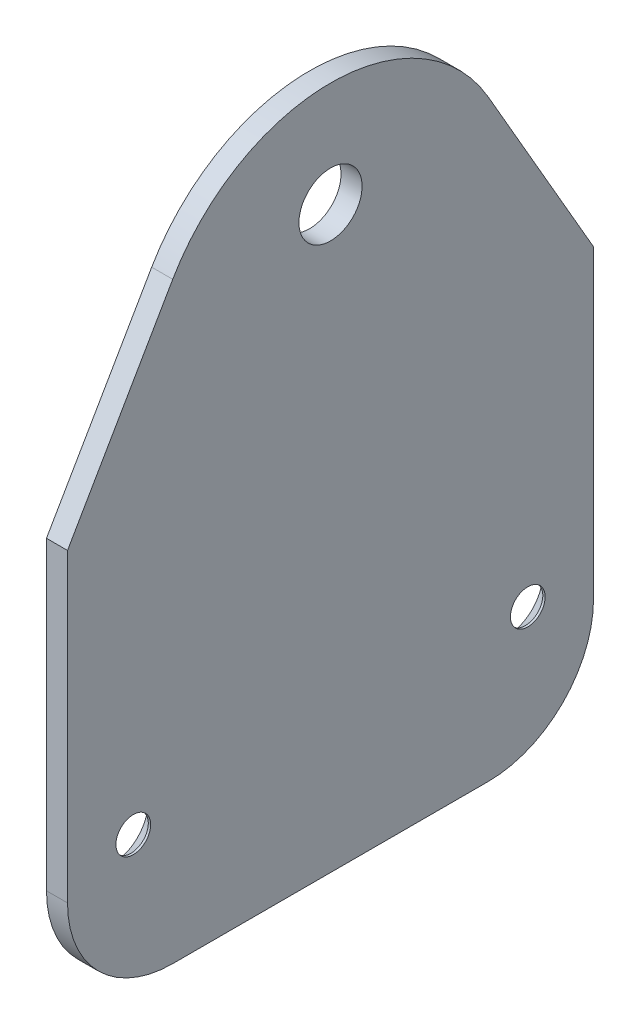
SolidWorks part; units mm, degrees
material "1023 Листовая углеродистая сталь (SS)"
ref_plane "Спереди" through (0, 0, 0) normal (0, 0, 1) x (1, 0, 0)
ref_plane "Сверху" through (0, 0, 0) normal (0, 1, 0) x (1, 0, 0)
ref_plane "Справа" through (0, 0, 0) normal (1, 0, 0) x (0, 0, -1)
sketch "Эскиз1" plane through (0, 0, 0) normal (0, 1, 0) x (1, 0, 0)
  line L1 (20, -45) -> (-20, -45)
  line L2 (20, -45) -> (20, 45)
  line L3 (20, 45) -> (-20, 45)
  line L4 (-20, -45) -> (-20, 45)
  line L5 (20, -45) -> (-20, 45) construction
  line L6 (20, 45) -> (-20, -45) construction
  point P0 (0, 0)
  dimension "D1" = 90
  dimension "D2" = 40
sketch "Эскиз10" plane through (0, 0, 0) normal (1, 0, 0) x (0, 0, -1)
  line L0 (2.2, 0) -> (-2.2, 0) construction
  line L1 (-50, 0) -> (50, 0)
  line L2 (-50, 0) -> (-50, 130)
  line L3 (-50, 130) -> (50, 130)
  line L4 (50, 0) -> (50, 130)
  line L5 (0, 0) -> (0, 50000) construction
  dimension "D1" = 100
  dimension "D2" = 130
base flange "Базовая кромка1" sketch "Эскиз10" thickness 4 reverse thickness direction no parameters "D1"=5
sketch "Эскиз13" plane through (-4, 0, 0) normal (-1, 0, 0) x (0, 0, 1)
  line L1 (-50, 130) -> (50, 130) construction
  circle A0 centre (0, 110) radius 6
  dimension "D2" = 12
  dimension "D1" = 20
extrude "Вырез-Вытянуть1" cut sketch "Эскиз13" against normal blind 10 normal cut yes
sketch "Эскиз17" plane through (-4, 0, 0) normal (-1, 0, 0) x (0, 0, 1)
  line L0 (50, 0) -> (-50, 0) construction
  line L2 (0, 68.9825) -> (0, -30.3252) construction
  point P0 (-37.5, 25)
  point P3 (37.5, 25)
  dimension "D1" = 75
  dimension "D2" = 25
hole_wizard "Зенковка для винта с потайной головкой и внутренним шестигранником M61" positions "Эскиз17" profile "Эскиз16" countersink size "M6" standard "DIN" end condition through all
sketch "Эскиз16" plane through (-4, 25, -37.5) normal (0, 1, 0) x (0, 0, 1)
  line L0 (0, 0) -> (0, 4)
  line L1 (0, 4) -> (3.3, 4)
  line L2 (3.3, 4) -> (3.3, 3.555)
  line L3 (3.3, 3.555) -> (6.855, 0)
  line L5 (6.855, 0) -> (0, 0)
  line L6 (-3.3, 3.555) -> (-6.855, 0) construction
  line L11 (0, -6.35) -> (0, 107.95) construction
  dimension "Диаметр сквозного отверстия" = 6.6
  dimension "Глубина сквозного отверстия" = 4
  dimension "Диаметр передней зенковки" = 13.71
  dimension "Угол передней зенковки" = 90
chamfer "Фаска1" distance 30 angle 60 2 edges at (-2, 130, 50) (-2, 130, -50) first distance on face at (-2, 130, 0)
fillet "Скругление1" radius 34.641 4 edges at (0, 130, 0) (-4, 130, 0) (-2, 130, -20) (-2, 130, 20)
fillet "Скругление2" radius 20 2 edges at (-2, 0, 50) (-2, 0, -50)
sketch "Сгиб-Линии1" [suppressed] plane through (0, 0, 0) normal (0, 1, 0) x (1, 0, 0)
sketch "Граничная рамка1" [suppressed] plane through (0, 0, 0) normal (0, 1, 0) x (1, 0, 0)
sheet metal parameters "Листовой металл4" thickness 4 parameters "D1"=5
flat pattern "Развертка4" [suppressed]
sketch "Сгиб-Линии3" plane through (0, 0, 0) normal (0, 1, 0) x (1, 0, 0)
sketch3d "Граничная рамка3" [suppressed]
  line L0 (-45, 120, 0) -> (-45, 0, 0) construction
  line L1 (45, 120, 0) -> (45, 0, 0) construction
  line L2 (-45, 120, 0) -> (45, 120, 0) construction
  line L3 (-45, 0, 0) -> (45, 0, 0) construction
sheet metal parameters "Листовой металл5" thickness 4 parameters "D1"=5
flat pattern "Развертка4"
sketch "Сгиб-Линии3" plane through (0, 0, 0) normal (0, 1, 0) x (1, 0, 0)
sketch3d "Граничная рамка3" [suppressed]
  line L0 (-45, 110, 0) -> (-45, 0, 0) construction
  line L1 (45, 110, 0) -> (45, 0, 0) construction
  line L2 (-45, 110, 0) -> (45, 110, 0) construction
  line L3 (-45, 0, 0) -> (45, 0, 0) construction
sheet metal parameters "Листовой металл7" thickness 4 parameters "D1"=5
flat pattern "Развертка4"
sketch "Сгиб-Линии3" plane through (0, 0, 0) normal (0, 1, 0) x (1, 0, 0)
sketch3d "Граничная рамка3" [suppressed]
  line L0 (-50, 0, 0) -> (-50, 130, 0) construction
  line L1 (50, 0, 0) -> (50, 130, 0) construction
  line L2 (-50, 0, 0) -> (50, 0, 0) construction
  line L3 (-50, 130, 0) -> (50, 130, 0) construction
